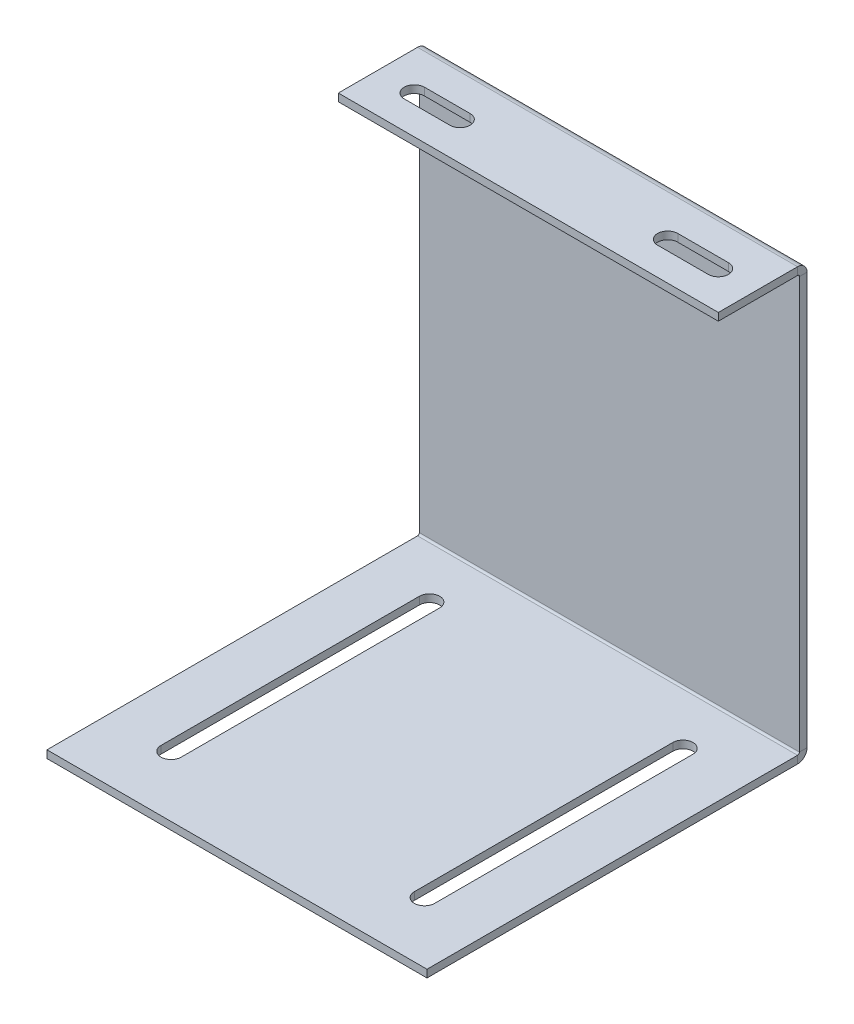
SolidWorks part; units mm, degrees
note: The reader was unsure of these and kept them because the rebuilt part matched: flange length of "Edge-Flange1", "Edge-Flange2".
material "Galvanized Steel"
ref_plane "Front Plane" through (0, 0, 0) normal (0, 0, 1) x (1, 0, 0)
ref_plane "Top Plane" through (0, 0, 0) normal (0, 1, 0) x (1, 0, 0)
ref_plane "Right Plane" through (0, 0, 0) normal (1, 0, 0) x (0, 0, -1)
sketch "Sketch1" plane through (0, 0, 0) normal (0, 1, 0) x (1, 0, 0)
  line L0 (-105.705, 4.9532) -> (-105.705, -97.0468) construction
  line L1 (19.295, 28.9532) -> (-130.705, 28.9532)
  line L2 (19.295, 28.9532) -> (19.295, -121.0468)
  line L3 (19.295, -121.0468) -> (-130.705, -121.0468)
  line L4 (-130.705, 28.9532) -> (-130.705, -121.0468)
  line L5 (-101.705, 4.9532) -> (-101.705, -97.0468)
  line L6 (-109.705, 4.9532) -> (-109.705, -97.0468)
  line L7 (-5.705, 4.9532) -> (-5.705, -97.0468) construction
  line L8 (-1.705, 4.9532) -> (-1.705, -97.0468)
  line L9 (-9.705, 4.9532) -> (-9.705, -97.0468)
  arc A0 (-101.705, 4.9532) -> (-109.705, 4.9532) centre (-105.705, 4.9532) ccw
  arc A1 (-109.705, -97.0468) -> (-101.705, -97.0468) centre (-105.705, -97.0468) ccw
  arc A2 (-1.705, 4.9532) -> (-9.705, 4.9532) centre (-5.705, 4.9532) ccw
  arc A3 (-9.705, -97.0468) -> (-1.705, -97.0468) centre (-5.705, -97.0468) ccw
  point P6 (-105.705, -46.0468)
  point P11 (-5.705, -46.0468)
  point P18 (-105.705, 8.9532)
  point P19 (-105.705, -101.0468)
  point P20 (-5.705, 8.9532)
  point P21 (-5.705, -101.0468)
  dimension "D1" = 150
  dimension "D2" = 150
  dimension "D3" = 8
  dimension "D4" = 8
  dimension "D5" = 24
  dimension "D6" = 110
  dimension "D7" = 110
  dimension "D8" = 25
  dimension "D9" = 25
base flange "Base-Flange1" sketch "Sketch1" thickness 3 reverse thickness direction no parameters "D1"=0.7366
edge flange "Edge-Flange1" sketch "Sketch8" flange angle 90 flange length 170 flange position material inside bend radius 0.7366 thickness 3 relief rectangular parameters "D6"=10
sketch "Sketch8" plane through (0, 0, -28.9532) normal (0, 0, 1) x (1, 0, 0)
  line L1 (19.295, 0) -> (-130.705, 0) construction
  line L2 (-130.705, 0) -> (-130.705, 167)
  line L3 (-130.705, 167) -> (19.295, 167)
  line L4 (19.295, 167) -> (19.295, 0)
  line L5 (19.295, 0) -> (-130.705, 0)
bend "EdgeBend1" bend radius 0.7366 bend angle 90 parameters "D5"=1
edge flange "Edge-Flange2" sketch "Sketch11" flange angle 90 flange length 35 flange position material inside bend radius 0.7366 thickness 3 relief rectangular parameters "D6"=10
sketch "Sketch11" plane through (0, 167, -25.9532) normal (0, -1, 0) x (1, 0, 0)
  line L1 (19.295, 0) -> (-130.705, 0) construction
  line L2 (-130.705, 0) -> (-130.705, 32)
  line L3 (-130.705, 32) -> (19.295, 32)
  line L4 (19.295, 32) -> (19.295, 0)
  line L5 (19.295, 0) -> (-130.705, 0)
bend "EdgeBend2" bend radius 0.7366 bend angle 90 parameters "D5"=2
sketch "Sketch12" plane through (0, 167, 0) normal (0, 1, 0) x (1, 0, 0)
  line L0 (19.295, 25.2166) -> (19.295, -6.0468) construction
  line L1 (-130.705, -6.0468) -> (-130.705, 25.2166) construction
  line L2 (-130.705, 28.9532) -> (19.295, 28.9532) construction
  line L3 (4.295, 4.9532) -> (-15.705, 4.9532)
  line L4 (-15.705, 12.9532) -> (4.295, 12.9532)
  line L5 (-115.705, 4.9532) -> (-97.6803, 4.9532)
  line L6 (-115.705, 12.9532) -> (-97.6803, 12.9532)
  arc A0 (-115.705, 12.9532) -> (-115.705, 4.9532) centre (-115.705, 8.9532) ccw
  arc A1 (4.295, 4.9532) -> (4.295, 12.9532) centre (4.295, 8.9532) ccw
  arc A2 (-97.6803, 4.9532) -> (-97.6803, 12.9532) centre (-97.6803, 8.9532) ccw
  arc A3 (-15.705, 12.9532) -> (-15.705, 4.9532) centre (-15.705, 8.9532) ccw
  dimension "D1" = 8
  dimension "D2" = 8
  dimension "D7" = 20
  dimension "D3" = 15
  dimension "D4" = 15
  dimension "D5" = 20
  dimension "D6" = 20
extrude "Cut-Extrude1" cut sketch "Sketch12" against normal blind 10 normal cut yes
sketch "Bend-Lines1" [suppressed] plane through (0, 0, 0) normal (0, 1, 0) x (1, 0, 0)
sketch "Bounding-Box1" [suppressed] plane through (0, 0, 0) normal (0, 1, 0) x (1, 0, 0)
sheet metal parameters "Sheet-Metal2" thickness 3 parameters "D1"=0.7366
flat pattern "Flat-Pattern2" [suppressed]
sketch "Bend-Lines2" plane through (0, 0, 0) normal (0, 1, 0) x (1, 0, 0)
sketch3d "Bounding-Box2" [suppressed]
  line L0 (-99.295, 28.9532, 0) -> (130.705, 28.9532, 0) construction
  line L1 (-99.295, -121.0468, 0) -> (130.705, -121.0468, 0) construction
  line L2 (-99.295, 28.9532, 0) -> (-99.295, -121.0468, 0) construction
  line L3 (130.705, 28.9532, 0) -> (130.705, -121.0468, 0) construction
sheet metal parameters "Sheet-Metal3" thickness 3 parameters "D1"=0.7366
flat pattern "Flat-Pattern2" [suppressed]
sketch "Bend-Lines2" plane through (0, 0, 0) normal (0, 1, 0) x (1, 0, 0)
  line L0 (99.295, 26.9733) -> (-130.705, 26.9733) construction
  line L1 (99.295, 26.9733) -> (-130.705, 26.9733) construction
sketch3d "Bounding-Box2" [suppressed]
  line L0 (-130.705, -121.0468, 0) -> (-130.705, 194.9933, 0) construction
  line L1 (99.295, -121.0468, 0) -> (99.295, 194.9933, 0) construction
  line L2 (-130.705, -121.0468, 0) -> (99.295, -121.0468, 0) construction
  line L3 (-130.705, 194.9933, 0) -> (99.295, 194.9933, 0) construction
bend of the flat pattern "Flatten-<EdgeBend1>1"
sheet metal parameters "Sheet-Metal4" thickness 3 parameters "D1"=0.7366
flat pattern "Flat-Pattern2"
sketch "Bend-Lines2" plane through (0, 0, 0) normal (0, 1, 0) x (1, 0, 0)
  line L0 (99.295, 26.9733) -> (-130.705, 26.9733) construction
  line L1 (99.295, 26.9733) -> (-130.705, 26.9733) construction
  line L4 (99.295, 193.0133) -> (-130.705, 193.0133) construction
  line L5 (99.295, 193.0133) -> (-130.705, 193.0133) construction
sketch3d "Bounding-Box2" [suppressed]
  line L0 (-130.705, -121.0468, 0) -> (-130.705, 221.0333, 0) construction
  line L1 (99.295, -121.0468, 0) -> (99.295, 221.0333, 0) construction
  line L2 (-130.705, -121.0468, 0) -> (99.295, -121.0468, 0) construction
  line L3 (-130.705, 221.0333, 0) -> (99.295, 221.0333, 0) construction
bend of the flat pattern "Flatten-<EdgeBend1>1"
bend of the flat pattern "Flatten-<EdgeBend2>1"
sheet metal parameters "Sheet-Metal5" thickness 3 parameters "D1"=0.7366
flat pattern "Flat-Pattern2"
sketch "Bend-Lines2" plane through (0, 0, 0) normal (0, 1, 0) x (1, 0, 0)
  line L0 (19.295, 26.9733) -> (-130.705, 26.9733) construction
  line L1 (19.295, 26.9733) -> (-130.705, 26.9733) construction
  line L4 (19.295, 193.0133) -> (-130.705, 193.0133) construction
  line L5 (19.295, 193.0133) -> (-130.705, 193.0133) construction
sketch3d "Bounding-Box2" [suppressed]
  line L0 (-130.705, -121.0468, 0) -> (-130.705, 226.0333, 0) construction
  line L1 (19.295, -121.0468, 0) -> (19.295, 226.0333, 0) construction
  line L2 (-130.705, -121.0468, 0) -> (19.295, -121.0468, 0) construction
  line L3 (-130.705, 226.0333, 0) -> (19.295, 226.0333, 0) construction
bend of the flat pattern "Flatten-<EdgeBend1>1"
bend of the flat pattern "Flatten-<EdgeBend2>1"
